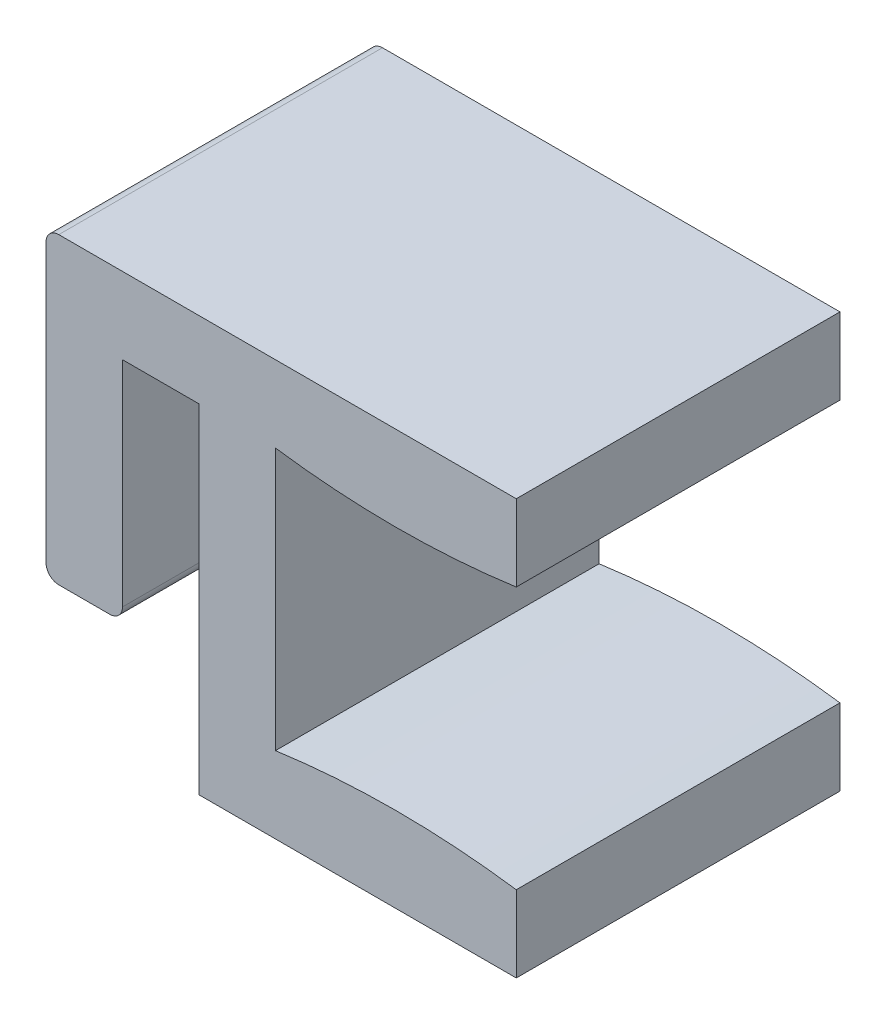
SolidWorks part; units mm, degrees
ref_plane "Front Plane" through (0, 0, 0) normal (0, 0, 1) x (1, 0, 0)
ref_plane "Top Plane" through (0, 0, 0) normal (0, 1, 0) x (1, 0, 0)
ref_plane "Right Plane" through (0, 0, 0) normal (1, 0, 0) x (0, 0, -1)
sketch "Sketch1" plane through (0, 0, 0) normal (0, 0, 1) x (1, 0, 0)
  line L2 (-159.7982, 9.1001) -> (-172.2482, 9.1001)
  line L3 (-172.2482, 9.1001) -> (-172.2482, -7.1851)
  line L7 (-169.2482, -22.8519) -> (-169.2482, 6.1001) construction
  line L12 (-169.2482, 5.72) -> (-169.2482, 2.545) construction
  line L23 (-159.7982, 6.1001) -> (-159.7982, 9.1001)
  line L28 (-164.5232, 5.77) -> (-144.5007, 5.77) construction
  line L29 (-156.5482, 5.72) -> (-169.2482, 5.72) construction
  line L30 (-169.2482, 6.1001) -> (-169.2482, 5.72)
  line L32 (-158.1026, 5.72) -> (-158.1026, -3.805) construction
  line L33 (-169.2482, -3.805) -> (-156.5482, -3.805) construction
  line L34 (-169.2482, 5.72) -> (-169.2482, -3.805)
  line L35 (-172.2482, 0.9575) -> (-169.2482, 0.9575) construction
  line L36 (-169.2482, -4.1851) -> (-169.2482, -3.805)
  line L37 (-159.7982, -4.1851) -> (-159.7982, -7.1851)
  line L38 (-159.7982, -7.1851) -> (-172.2482, -7.1851)
  line L39 (-159.7982, 5.72) -> (-159.7982, 2.545) construction
  arc A5 (-169.2482, 6.1001) -> (-159.7982, 6.1001) centre (-164.5232, 39.752) ccw
  arc A6 (-169.2482, -4.1851) -> (-159.7982, -4.1851) centre (-164.5232, -37.837) cw
  point P18 (-158.1026, 0.9575)
  dimension "D4" = 3
  dimension "D3" = 3
  dimension "D1" = 0.05
extrude "MainBody" add sketch "Sketch1" along normal blind 12.7
sketch "Sketch6" plane through (0, 0, 12.7) normal (0, 0, 1) x (1, 0, 0)
  line L0 (-172.2482, 9.1001) -> (-177.7482, 9.1001)
  line L1 (-172.2482, 9.1001) -> (-172.2482, -7.1851) construction
  line L6 (-172.2482, 6.1001) -> (-172.2482, 9.1001)
  line L7 (-178.2482, 8.6001) -> (-178.2482, -2.3019)
  line L8 (-177.7482, -2.8019) -> (-175.7482, -2.8019)
  line L9 (-175.2482, -2.3019) -> (-175.2482, 6.1001)
  line L10 (-175.2482, 6.1001) -> (-172.2482, 6.1001)
  line L12 (-159.7982, 9.1001) -> (-172.2482, 9.1001) construction
  arc A4 (-175.7482, -2.8019) -> (-175.2482, -2.3019) centre (-175.7482, -2.3019) ccw
  arc A5 (-178.2482, -2.3019) -> (-177.7482, -2.8019) centre (-177.7482, -2.3019) ccw
  arc A6 (-177.7482, 9.1001) -> (-178.2482, 8.6001) centre (-177.7482, 8.6001) ccw
  point P11 (-175.2482, -2.8019)
  point P15 (-178.2482, -2.8019)
  dimension "D3" = 3
  dimension "D5" = 0.5
  dimension "D1" = 3
  dimension "D2" = 3
extrude "Hook" add sketch "Sketch6" against normal up to surface (12.7 mm away) up to face at (-165.2732, 0.9575, 0)
equation "\"HookThicknes\"= 5"
equation "\"HookThickness\"=3"
equation "\"HookOverhang\"=3"
equation "\"HookHeight\"=5"
equation "\"D3@Sketch1\"=\"HookThickness\""
equation "\"D4@Sketch1\"=\"HookThickness\""
equation "\"D1@Sketch6\"=\"HookThickness\""
equation "\"D2@Sketch6\"=\"HookThickness\""
equation "\"D3@Sketch6\"=\"HookOverhang\""
